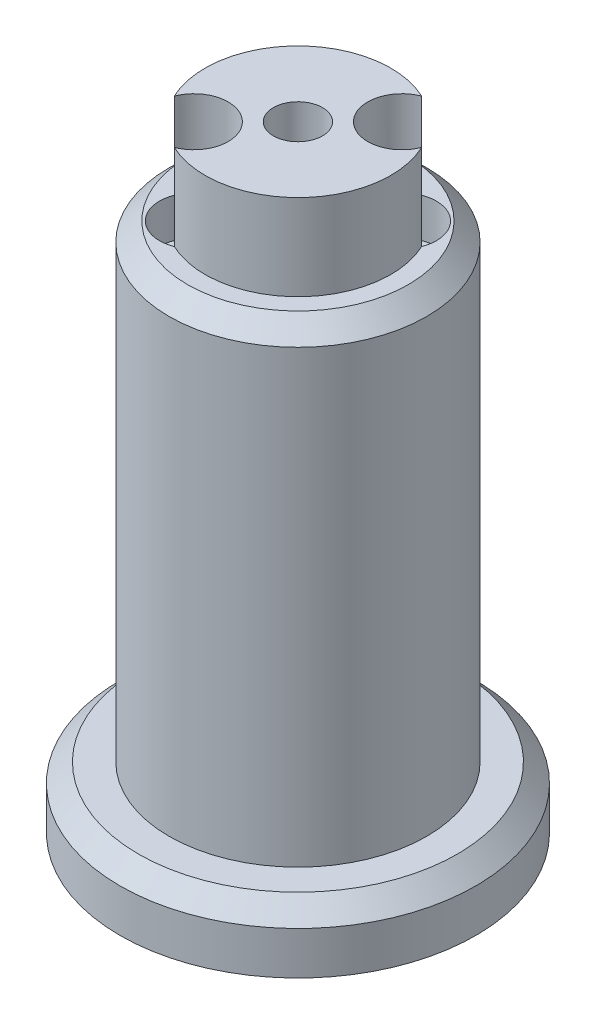
SolidWorks part; units mm, degrees
material "3DP Resin"
ref_plane "Front Plane" through (0, 0, 0) normal (0, 0, 1) x (1, 0, 0)
ref_plane "Top Plane" through (0, 0, 0) normal (0, 1, 0) x (1, 0, 0)
ref_plane "Right Plane" through (0, 0, 0) normal (1, 0, 0) x (0, 0, -1)
sketch "Sketch1" plane through (0, 0, 0) normal (0, 1, 0) x (1, 0, 0)
  circle A0 centre (0, 0) radius 14.5
  dimension "D1" = 29
extrude "Boss-Extrude1" add sketch "Sketch1" along normal blind 5
sketch "Sketch2" plane through (0, 0, 0) normal (0, -1, 0) x (1, 0, 0)
  circle A0 centre (0, 0) radius 13
  dimension "D1" = 26
extrude "Cut-Extrude1" cut sketch "Sketch2" against normal blind 3
sketch "Sketch6" plane through (0, 5, 0) normal (0, 1, 0) x (1, 0, 0)
  circle A0 centre (0, 0) radius 10.5
  dimension "D1" = 21
extrude "Boss-Extrude3" add sketch "Sketch6" along normal blind 45.2
sketch "Sketch3" plane through (0, 5, 0) normal (0, 1, 0) x (1, 0, 0)
  line L0 (14.5, 0) -> (-14.5, 0) construction
  line L1 (0, -14.5) -> (0, 14.5) construction
  line L2 (-4.2426, 4.2426) -> (0, 0) construction
  circle A0 centre (0, 0) radius 3
  circle A1 centre (0, 0) radius 14.5 construction
  circle A2 centre (0, 0) radius 6 construction
  circle A3 centre (-4.2426, 4.2426) radius 1.5
  circle A5 centre (4.2426, 4.2426) radius 1.5
  circle A6 centre (4.2426, -4.2426) radius 1.5
  circle A7 centre (-4.2426, -4.2426) radius 1.5
  point P7 (0, 0)
  point P11 (0, 0)
  point P14 (6.2887, -7.23)
  point P15 (0, 0)
  point P23 (0, 0)
  dimension "D1" = 6
  dimension "D2" = 12
  dimension "D3" = 3
  dimension "D4" = 45
  dimension "D5" = 4
extrude "Cut-Extrude2" cut sketch "Sketch3" along normal blind 5 from surface starting at face at (0, 3, -13)
sketch "Sketch7" plane through (0, 50.2, 0) normal (0, 1, 0) x (1, 0, 0)
  circle A0 centre (0, 0) radius 10.5
  circle A1 centre (0, 0) radius 7.575
  dimension "D1" = 15.15
  dimension "D2" = 21
extrude "Bearing Support" cut sketch "Sketch7" against normal blind 7
sketch "Sketch8" plane through (0, 3, 0) normal (0, -1, 0) x (1, 0, 0)
  line L0 (-13, 0) -> (13, 0) construction
  line L1 (0, -13) -> (0, 13) construction
  line L2 (-4.2426, 4.2426) -> (0, 0) construction
  line L3 (0, 0) -> (4.2426, -4.2426) construction
  circle A0 centre (0, 0) radius 2
  circle A1 centre (0, 0) radius 13 construction
  circle A2 centre (0, 0) radius 13 construction
  circle A3 centre (-4.2426, 4.2426) radius 1.5
  circle A4 centre (0, 0) radius 6 construction
  circle A5 centre (4.2426, -4.2426) radius 1.5
  circle A6 centre (-4.2426, 4.2426) radius 1.5 construction
  point P6 (0, 0)
  point P31 (0, 0)
  dimension "D1" = 4
  dimension "D2" = 3
  dimension "D3" = 12
  dimension "D4" = 45
extrude "M4 Hole Bore" cut sketch "Sketch8" against normal through all
sketch "Sketch9" plane through (0, 50.2, 0) normal (0, 1, 0) x (1, 0, 0)
  circle A0 centre (4.2426, 4.2426) radius 1.5 construction
  circle A1 centre (-4.2426, -4.2426) radius 1.5 construction
  circle A2 centre (4.2426, 4.2426) radius 1.5 construction
  circle A3 centre (-4.2426, -4.2426) radius 1.5 construction
  circle A4 centre (4.2426, 4.2426) radius 2.8
  circle A5 centre (-4.2426, -4.2426) radius 2.8
  dimension "D1" = 5.6
extrude "M3 Bolt Recesses" cut sketch "Sketch9" against normal blind 10.2
chamfer "Chamfer1" distance 1.5 angle 45 2 edges at (0, 43.2, 10.5) (0, 5, 14.5)
